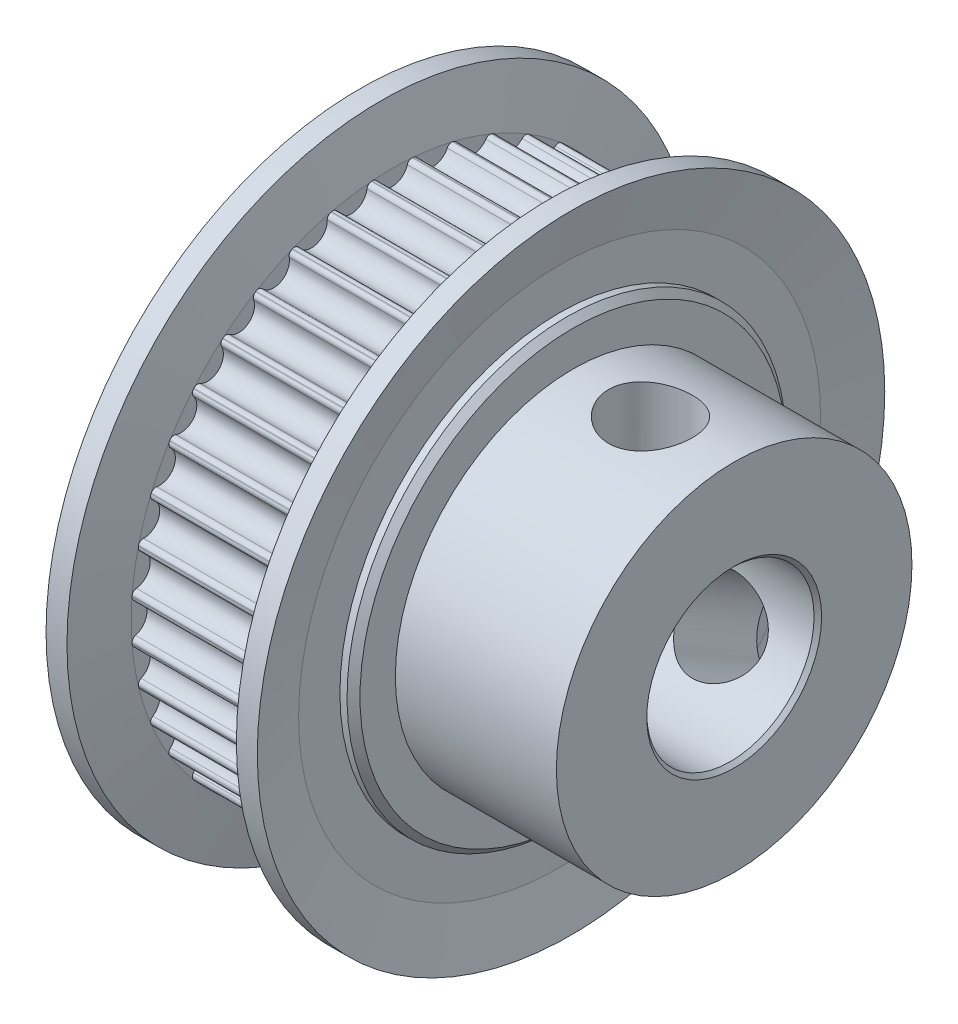
SolidWorks part; units mm, degrees
ref_plane "前视基准面" through (0, 0, 0) normal (0, 0, 1) x (1, 0, 0)
ref_plane "上视基准面" through (0, 0, 0) normal (0, 1, 0) x (1, 0, 0)
ref_plane "右视基准面" through (0, 0, 0) normal (1, 0, 0) x (0, 0, -1)
sketch "草图1" plane through (0, 0, 0) normal (1, 0, 0) x (0, 0, -1)
  line L0 (0, 0) -> (40, 0)
  line L1 (0, 0) -> (0, 12.73) construction
  line L5 (0, 0) -> (11.0245, -6.365) construction
  line L6 (-1.5, 3.7081) -> (1.5, 3.7081)
  line L7 (-1.5, 3.7081) -> (-1.5, 5.4)
  line L8 (-1.5, 5.4) -> (1.5, 5.4)
  line L9 (1.5, 3.7081) -> (1.5, 5.4)
  circle A0 centre (0, 0) radius 12.73
  arc A1 (-0.9608, 12.4379) -> (12.475, 0) centre (0, 0) ccw
  arc A3 (-0.9608, 12.4379) -> (-0.7218, 12.2711) centre (-0.9431, 12.2086) cw
  arc A5 (0.9608, 12.4379) -> (0.7218, 12.2711) centre (0.9431, 12.2086) ccw
  circle A6 centre (0, 0) radius 4
  arc A7 (-0.7218, 12.2711) -> (0.7218, 12.2711) centre (0, 12.475) ccw
  point P8 (0, 11.725)
  point P20 (0, 12.475)
  point P26 (0, 4)
  dimension "D1" = 0.75
  dimension "Dr" = 25.46
  dimension "Ds" = 24.95
  dimension "D4" = 0.23
  dimension "dH7" = 8
  dimension "Z" = 40
  dimension "t" = 1.4
  dimension "b" = 3
  dimension "角度" = 120
sketch "草图2" plane through (0, 0, 0) normal (0, 0, 1) x (1, 0, 0)
  line L0 (0, 0) -> (10.3, 0) construction
  line L1 (0, 0) -> (0, 10.5)
  line L2 (0, 10.5) -> (1.65, 10.5)
  line L3 (1.65, 10.5) -> (1.65, 12.475)
  line L4 (1.65, 12.475) -> (8.65, 12.475)
  line L5 (8.65, 12.475) -> (8.65, 10.5)
  line L6 (8.65, 10.5) -> (10.3, 10.5)
  line L7 (10.3, 10.5) -> (10.3, 0)
  line L8 (0, 0) -> (0, 12.73) construction
  line L9 (0.65, 10.5) -> (0.65, 12.475)
  line L10 (0.65, 12.475) -> (0.1, 15)
  line L11 (0.1, 15) -> (1.1, 15)
  line L12 (1.1, 15) -> (1.65, 12.475)
  line L13 (1.65, 12.475) -> (1.65, 10.5)
  line L14 (14, 8.5) -> (14, 0) construction
  line L15 (16, 12.475) -> (16, 0)
  line L16 (10.3, 8.5) -> (18, 8.5)
  line L18 (9, 4) -> (0, 4)
  line L19 (18, 8.5) -> (18, 0)
  line L20 (9, 3.5) -> (18, 3.5)
  line L21 (11.7744, 8.5) -> (11.7744, 3.5) construction
  point P27 (9, 3.5)
  point P36 (15.6244, 8.5)
  point P37 (5.15, 0)
  dimension "D1" = 3.85
  dimension "A" = 7
  dimension "W" = 10.3
  dimension "Dfi" = 21
  dimension "D2" = 1.55
  dimension "D3" = 1
  dimension "Dfo" = 30
  dimension "M" = 4
  dimension "S" = 9
  dimension "Dsh7" = 7
  dimension "L" = 18
  dimension "D" = 17
  dimension "D4" = 4
  dimension "FC" = 5.3244
sketch "草图3" plane through (0, 0, 0) normal (0, 0, 1) x (1, 0, 0)
  line L0 (0, 0) -> (0, 10.19)
  line L1 (0.31, 10.5) -> (1.65, 10.5)
  line L2 (1.65, 10.5) -> (1.65, 12.475)
  line L3 (1.65, 12.475) -> (8.65, 12.475)
  line L4 (8.65, 12.475) -> (8.65, 10.5)
  line L5 (8.65, 10.5) -> (9.99, 10.5)
  line L6 (10.3, 10.19) -> (10.3, 0)
  line L7 (10.3, 0) -> (0, 0)
  line L8 (0, 10.19) -> (0.31, 10.5)
  line L9 (9.99, 10.5) -> (10.3, 10.19)
  point P1 (0, 10.5)
  point P13 (10.3, 10.5)
  dimension "D1" = 0.31
  dimension "D2" = 45
  dimension "D4" = 45
revolve "旋转1" add sketch "草图3" angle 360 about L7
sketch "草图20" plane through (0, 0, 0) normal (0, 0, 1) x (1, 0, 0)
  line L0 (10.3, 8.5) -> (18, 8.5) construction
  line L1 (18, 0) -> (9.65, 0)
  line L2 (18, 0) -> (18, 8.5)
  line L3 (18, 8.5) -> (9.65, 8.5)
  line L4 (9.65, 0) -> (9.65, 8.5)
  line L6 (8.65, 12.475) -> (8.65, 10.5) construction
  dimension "D1" = 1
revolve "旋转5" add sketch "草图20" angle 360 mid plane about L1
sketch "草图4" plane through (0, 0, 0) normal (1, 0, 0) x (0, 0, -1)
  arc A1 (0.9608, 12.4379) -> (0.7218, 12.2711) centre (0.9431, 12.2086) ccw construction
  arc A3 (-0.7218, 12.2711) -> (-0.9608, 12.4379) centre (-0.9431, 12.2086) ccw construction
  arc A4 (-0.7218, 12.2711) -> (0.7218, 12.2711) centre (0, 12.475) ccw construction
  arc A5 (0.9608, 12.4379) -> (0.7218, 12.2711) centre (0.9431, 12.2086) ccw
  arc A6 (-0.7218, 12.2711) -> (0.7218, 12.2711) centre (0, 12.475) ccw
  arc A7 (-0.7218, 12.2711) -> (-0.9608, 12.4379) centre (-0.9431, 12.2086) ccw
  arc A8 (-0.9608, 12.4379) -> (12.475, 0) centre (0, 0) ccw construction
  arc A9 (0.9608, 12.4379) -> (-0.9608, 12.4379) centre (0, 0) ccw
extrude "切除-拉伸1" cut sketch "草图4" along normal up to vertex (8.65 mm away) from vertex up to point (8.65, 12.475, 0) starting at point (1.65, 12.475, 0)
pattern_circular "阵列(圆周)1" count 40 over 360 about axis through (10.3, 0, 0) along (1, 0, 0) of "切除-拉伸1"
sketch "草图5" plane through (0, 0, 0) normal (0, 0, 1) x (1, 0, 0)
  line L0 (1.1, 15) -> (1.65, 12.475) construction
  line L1 (0.1, 15) -> (1.1, 15) construction
  line L2 (0.65, 12.475) -> (0.1, 15) construction
  line L3 (0.65, 10.5) -> (0.65, 12.475) construction
  line L4 (1.65, 10.5) -> (1.65, 12.475) construction
  line L5 (1.1, 15) -> (1.65, 12.475)
  line L6 (0.1, 15) -> (1.1, 15)
  line L7 (0.65, 12.475) -> (0.1, 15)
  line L8 (0.65, 10.5) -> (0.65, 12.475)
  line L9 (1.65, 10.5) -> (1.65, 12.475)
  line L10 (0.65, 10.5) -> (1.65, 10.5)
  line L11 (0, 0) -> (10.3, 0) construction
  line L12 (5.15, 0) -> (5.15, 12.475) construction
  line L13 (9.65, 10.5) -> (8.65, 10.5)
  line L14 (9.65, 10.5) -> (9.65, 12.475)
  line L15 (9.65, 12.475) -> (10.2, 15)
  line L16 (10.2, 15) -> (9.2, 15)
  line L17 (9.2, 15) -> (8.65, 12.475)
  line L18 (8.65, 10.5) -> (8.65, 12.475)
  line L19 (1.65, 12.475) -> (8.65, 12.475) construction
revolve "旋转2" add sketch "草图5" angle 360 about L11
sketch "草图6" plane through (0, 0, 0) normal (1, 0, 0) x (0, 0, -1)
  circle A0 centre (0, 0) radius 4 construction
  circle A1 centre (0, 0) radius 4
extrude "切除-拉伸2" cut sketch "草图6" along normal through all
chamfer "倒角1" distance 0.18 angle 45 2 edges at (0, 0, -4) (18, 0, -4)
sketch "草图7" [suppressed] plane through (0, 0, 0) normal (1, 0, 0) x (0, 0, -1)
  line L0 (-3, 9.5394) -> (3, 9.5394) construction
  line L1 (3, 9.5394) -> (3, 12.8) construction
  line L2 (-3, 12.8) -> (3, 12.8) construction
  line L3 (-3, 9.5394) -> (-3, 12.8) construction
  line L4 (-3, 9.5394) -> (3, 9.5394)
  line L5 (3, 9.5394) -> (3, 12.8)
  line L6 (-3, 12.8) -> (3, 12.8)
  line L7 (-3, 9.5394) -> (-3, 12.8)
extrude "键槽孔1" [suppressed] cut sketch "草图7" along normal up to vertex
sketch "草图8" [suppressed] plane through (0, 0, 0) normal (0, 0, 1) x (1, 0, 0)
  line L0 (19, 10) -> (0, 10) construction
  line L1 (19, 3.5) -> (28, 3.5) construction
  line L2 (19, 10) -> (0, 10)
  line L4 (19, 3.5) -> (28, 3.5)
  line L7 (28, 0) -> (29, 0)
  line L8 (0, 0) -> (28, 0)
  line L10 (0, 10) -> (-1, 10)
  line L11 (-1, 10) -> (-1, 0)
  line L12 (-1, 0) -> (0, 0)
  line L13 (29, 0) -> (29, 3.5)
  line L14 (29, 3.5) -> (28, 3.5)
  dimension "D1" = 1
  dimension "D2" = 1
sketch "草图28" [suppressed] plane through (0, 0, 0) normal (0, 0, 1) x (1, 0, 0)
  line L0 (19, 10) -> (19, 0)
  line L1 (0, 0) -> (20, 0) construction
  line L2 (19, 0) -> (-1, 0)
  line L4 (-1, 10) -> (-1, 0) construction
  line L5 (-1, 10) -> (-1, 0)
  line L6 (-1, 10) -> (19, 10)
revolve "切除-旋转8" [suppressed] cut sketch "草图28" angle 360 about L2
sketch "草图30" [suppressed] plane through (0, 0, 0) normal (0, 0, 1) x (1, 0, 0)
  line L0 (19, 3.5) -> (19, 0)
  line L1 (0, 0) -> (20, 0) construction
  line L2 (29, 0) -> (29, 3.5) construction
  line L3 (29, 0) -> (29, 3.5)
  line L4 (19, 3.5) -> (29, 3.5)
  line L5 (19, 0) -> (29, 0)
revolve "切除-旋转9" [suppressed] cut sketch "草图30" angle 360 about L5
chamfer "倒角2" [suppressed] distance 0.17 angle 45
sketch "草图18" [suppressed] plane through (0, 0, 0) normal (0, 0, 1) x (1, 0, 0)
  line L1 (28, 11) -> (28, 0) construction
  line L2 (9, 10) -> (28, 10)
  line L3 (28, 10) -> (28, 0)
  line L4 (28, 0) -> (0, 0)
  line L5 (0, 0) -> (0, 3.5)
  line L7 (19, 10) -> (0, 10) construction
  line L8 (0, 0) -> (0, 13.5) construction
  line L9 (0, 3.5) -> (9, 3.5)
  line L12 (19, 3.5) -> (28, 3.5) construction
sketch "草图31" [suppressed] plane through (0, 0, 0) normal (0, 0, 1) x (1, 0, 0)
  line L1 (0, 0) -> (0, 3.5) construction
  line L2 (0, 3.5) -> (9, 3.5)
  line L3 (0, 0) -> (0, 3.5)
  line L4 (9, 3.5) -> (9, 0)
  line L5 (28, 0) -> (0, 0) construction
  line L6 (9, 0) -> (0, 0)
revolve "切除-旋转10" [suppressed] cut sketch "草图31" angle 360 about L6
sketch "草图32" [suppressed] plane through (0, 0, 0) normal (0, 0, 1) x (1, 0, 0)
  line L0 (9, 10) -> (28, 10) construction
  line L1 (9, 10) -> (28, 10)
  line L2 (28, 10) -> (28, 0) construction
  line L3 (28, 10) -> (28, 0)
  line L4 (28, 0) -> (9, 0)
  line L5 (28, 0) -> (0, 0) construction
  line L6 (9, 0) -> (9, 10)
revolve "切除-旋转11" [suppressed] cut sketch "草图32" angle 360 about L4
chamfer "倒角3" [suppressed] distance 0.17 angle 45
sketch "追加工草图" plane through (0, 0, 0) normal (1, 0, 0) x (0, 0, -1)
  circle A0 centre (0, 0) radius 5
  circle A1 centre (0, 5) radius 1
  point P5 (10, 0)
  dimension "D1" = 10
  dimension "TH" = 10
  dimension "MZ" = 2
sketch "草图23" [suppressed] plane through (0, 0, 0) normal (0, 0, 1) x (1, 0, 0)
  line L0 (0, 0) -> (16.8867, 0) construction
  line L1 (8, 8.75) -> (16.8867, 8.75)
  line L2 (8, 8.75) -> (8, 7.5)
  line L3 (8, 7.5) -> (16.8867, 7.5)
  line L4 (16.8867, 8.75) -> (16.8867, 7.5)
revolve "切除-旋转7" [suppressed] cut sketch "草图23" angle 360 mid plane about L0
sketch "草图24" [suppressed] plane through (0, 0, 0) normal (0, 0, 1) x (1, 0, 0)
  line L0 (16.8867, 3.5) -> (7.9342, 3.5)
  line L1 (7.9342, 3.5) -> (8, 10.74)
  line L2 (8, 10.74) -> (7.4534, 7.5)
  line L3 (7.4534, 7.5) -> (16.8867, 7.5)
  line L4 (16.8867, 7.5) -> (16.8867, 3.5)
  line L5 (0, 0) -> (16.8867, 0) construction
  line L6 (0, -2.5) -> (0, 2.5) construction
revolve "旋转8" [suppressed] add sketch "草图24" angle 360 mid plane about L5
chamfer "倒角4" [suppressed] distance 0.18 angle 45
sketch "草图25" plane through (0, 0, 0) normal (0, 1, 0) x (1, 0, 0)
  circle A0 centre (14, 0) radius 2
  dimension "D1" = 4
extrude "切除-拉伸3" cut sketch "草图25" along normal through all
cosmetic thread "装饰螺纹线1" parameters "D2"=4.1
pattern_circular "阵列(圆周)2" count 2 every 120 about axis through (18, 0, 0) along (1, 0, 0) of "切除-拉伸3" reverse direction yes
sketch "草图26" [suppressed] plane through (0, 0, 0) normal (0, 0, 1) x (1, 0, 0)
  line L0 (16.8867, 0) -> (18.4491, 0) construction
  line L1 (15.3244, 7.5) -> (18.4491, 7.5)
  line L2 (15.3244, 7.5) -> (15.3244, -7.5)
  line L3 (15.3244, -7.5) -> (18.4491, -7.5)
  line L4 (18.4491, 7.5) -> (18.4491, -7.5)
extrude "切除-拉伸4" [suppressed] cut sketch "草图26" against normal through all and the other way through all
chamfer "倒角6" [suppressed] distance 0.18 angle 45
sketch "草图12" plane through (0, 0, 0) normal (1, 0, 0) x (0, 0, -1)
  circle A0 centre (0, 5) radius 1 construction
  circle A1 centre (0, 5) radius 1
  circle A2 centre (4.3301, 2.5) radius 1
  circle A3 centre (4.3301, -2.5) radius 1
  circle A4 centre (0, -5) radius 1
  circle A5 centre (-4.3301, -2.5) radius 1
  circle A6 centre (-4.3301, 2.5) radius 1
  circle A7 centre (0, 0) radius 5 construction
  dimension "D1" = 6
extrude "SH6" [suppressed] cut sketch "草图12" along normal through all
sketch "草图13" plane through (0, 0, 0) normal (1, 0, 0) x (0, 0, -1)
  circle A0 centre (0, 5) radius 1 construction
  circle A1 centre (0, 5) radius 1
  circle A2 centre (5, 0) radius 1
  circle A3 centre (0, -5) radius 1
  circle A4 centre (-5, 0) radius 1
  circle A5 centre (0, 0) radius 5 construction
  dimension "D1" = 4
extrude "SH4" [suppressed] cut sketch "草图13" along normal through all
sketch "草图14" plane through (0, 0, 0) normal (1, 0, 0) x (0, 0, -1)
  circle A0 centre (0, 5) radius 1 construction
  circle A1 centre (0, 5) radius 1
  circle A2 centre (4.3301, -2.5) radius 1
  circle A3 centre (-4.3301, -2.5) radius 1
  circle A4 centre (0, 0) radius 5 construction
  dimension "D1" = 3
extrude "SH3" [suppressed] cut sketch "草图14" along normal through all
sketch "草图15" plane through (0, 0, 0) normal (1, 0, 0) x (0, 0, -1)
  circle A0 centre (0, 5) radius 1 construction
  circle A1 centre (0, 5) radius 1
  circle A2 centre (4.3301, 2.5) radius 1
  circle A3 centre (4.3301, -2.5) radius 1
  circle A4 centre (0, -5) radius 1
  circle A5 centre (-4.3301, -2.5) radius 1
  circle A6 centre (-4.3301, 2.5) radius 1
  circle A7 centre (0, 0) radius 5 construction
  dimension "D1" = 6
extrude "TH6" [suppressed] cut sketch "草图15" against normal blind 2 from vertex
sketch "草图16" plane through (0, 0, 0) normal (1, 0, 0) x (0, 0, -1)
  circle A0 centre (0, 5) radius 1 construction
  circle A1 centre (0, 5) radius 1
  circle A2 centre (5, 0) radius 1
  circle A3 centre (0, -5) radius 1
  circle A4 centre (-5, 0) radius 1
  circle A5 centre (0, 0) radius 5 construction
  dimension "D1" = 4
extrude "TH4" [suppressed] cut sketch "草图16" against normal blind 2 from vertex
sketch "草图17" plane through (0, 0, 0) normal (1, 0, 0) x (0, 0, -1)
  circle A0 centre (0, 5) radius 1 construction
  circle A1 centre (0, 5) radius 1
  circle A2 centre (4.3301, -2.5) radius 1
  circle A3 centre (-4.3301, -2.5) radius 1
  circle A4 centre (0, 0) radius 5 construction
  dimension "D1" = 3
extrude "TH3" [suppressed] cut sketch "草图17" against normal blind 2 from vertex
